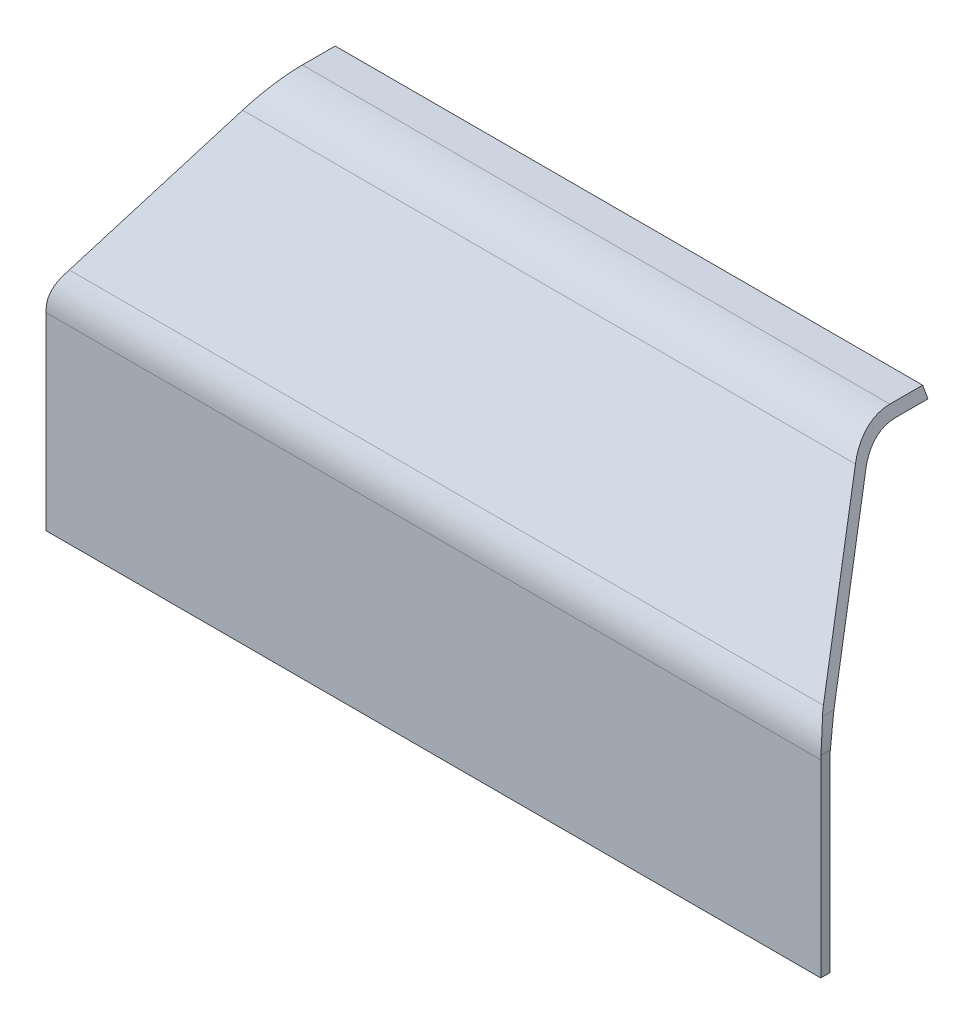
SolidWorks part; units mm, degrees
ref_plane "Alzado" through (0, 0, 0) normal (0, 0, 1) x (1, 0, 0)
ref_plane "Planta" through (0, 0, 0) normal (0, 1, 0) x (1, 0, 0)
ref_plane "Vista lateral" through (0, 0, 0) normal (1, 0, 0) x (0, 0, -1)
sketch "Croquis1" plane through (0, 0, 0) normal (1, 0, 0) x (0, 0, -1)
  line L0 (0, 0) -> (0, 66.9081)
  line L1 (0, 66.9081) -> (41.9998, 116.9615)
  line L2 (41.9998, 116.9615) -> (60.6009, 116.9615)
  line L3 (60.6009, 116.9615) -> (60.6009, 119.9615)
  line L4 (60.6009, 119.9615) -> (40.6009, 119.9615)
  line L5 (40.6009, 119.9615) -> (-3, 68)
  line L6 (-3, 68) -> (-3, 0)
  line L7 (-3, 0) -> (0, 0)
  line L8 (0, 66.9081) -> (29.2398, 66.9081) construction
  dimension "D1" = 3
  dimension "D2" = 3
  dimension "D3" = 3
  dimension "D4" = 68
  dimension "D5" = 119.9615
  dimension "D6" = 20
  dimension "D7" = 50
extrude "Saliente-Extruir1" add sketch "Croquis1" along normal mid plane 252
fillet "Redondeo1" radius 18 1 edges at (0, 68, 3)
fillet "Redondeo2" radius 20 1 edges at (0, 119.9615, -40.6009)
fillet "Redondeo3" radius 17 1 edges at (0, 116.9615, -41.9998)
fillet "Redondeo4" radius 17 1 edges at (0, 66.9081, 0)
sketch "Croquis2" plane through (0, 0, 3) normal (0, 0, 1) x (1, 0, 0)
  line L8 (-126, 0) -> (-126, 62.641)
  line L13 (-123.7224, 71.141) -> (-95.5359, 119.9615)
  line L18 (-129, 68) -> (-129, 0)
  line L19 (-129, 0) -> (-126, 0)
  line L20 (-126, 67.1962) -> (-96.7602, 67.1962) construction
  line L21 (-126, 61.4485) -> (-126, 0) construction
  line L22 (126, 0) -> (-126, 0) construction
  line L23 (-129, 68) -> (-129, 119.9615)
  line L25 (-129, 119.9615) -> (-95.5359, 119.9615)
  line L26 (-126, 119.9615) -> (126, 119.9615) construction
  arc A2 (-126, 62.641) -> (-123.7224, 71.141) centre (-109, 62.641) cw
  dimension "D8" = 17
  dimension "D3" = 3
  dimension "D4" = 68
  dimension "D7" = 60
extrude "Cortar-Extruir1" cut sketch "Croquis2" against normal through all
mirror "Simetría1" about plane through (0, 0, 0) normal (1, 0, 0) of "Cortar-Extruir1"
